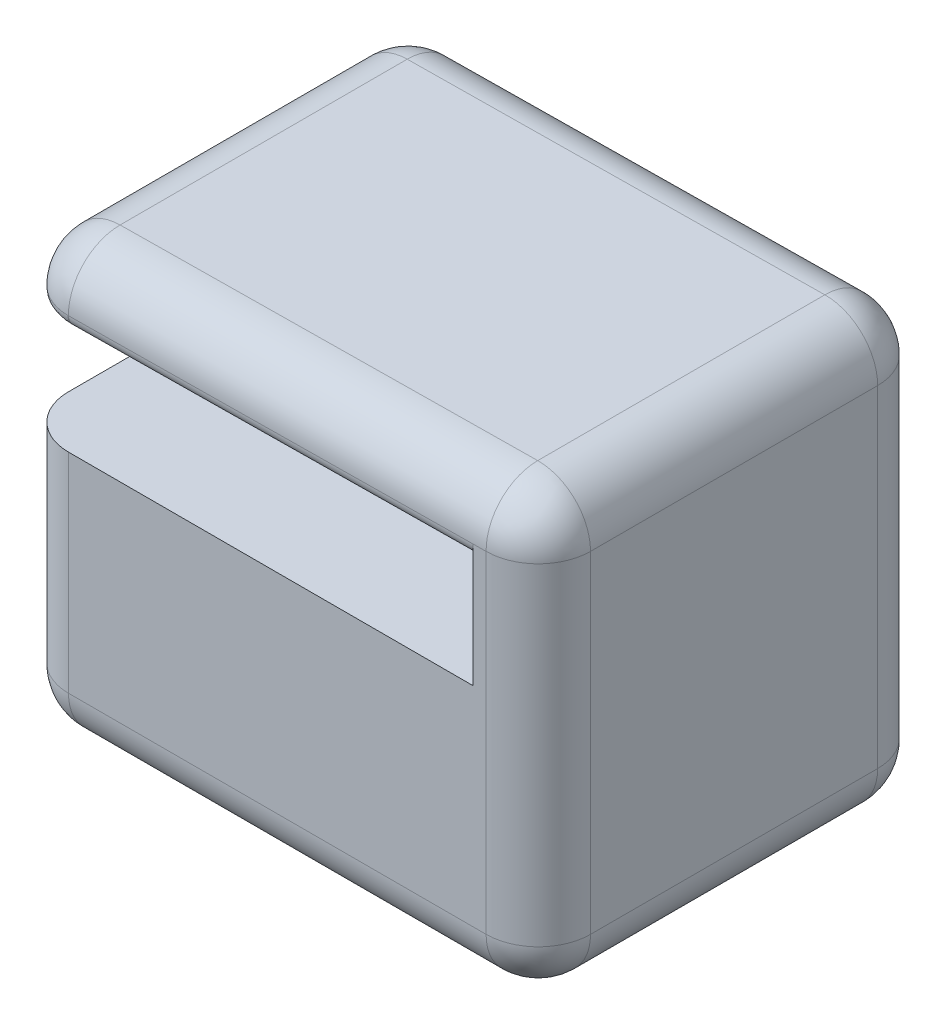
SolidWorks part; units mm, degrees
ref_plane "Front Plane" through (0, 0, 0) normal (0, 0, 1) x (1, 0, 0)
ref_plane "Top Plane" through (0, 0, 0) normal (0, 1, 0) x (1, 0, 0)
ref_plane "Right Plane" through (0, 0, 0) normal (1, 0, 0) x (0, 0, -1)
sketch "Sketch1" plane through (0, 0, 0) normal (0, 0, 1) x (1, 0, 0)
  line L1 (0, -10.6226) -> (-25.3983, -10.6226)
  line L2 (0, -10.6226) -> (0, 10.6226)
  line L3 (0, 10.6226) -> (-25.3983, 10.3324)
  line L4 (-25.3983, -10.6226) -> (-25.3983, 10.3324)
  line L5 (-25.3983, 7.1574) -> (-3.175, 7.1574) construction
  line L6 (-25.3983, 7.1574) -> (-25.3983, 2.0774) construction
  line L7 (-25.3983, 2.0774) -> (-3.175, 2.0774) construction
  line L8 (-3.175, 7.1574) -> (-3.175, 2.0774) construction
  line L12 (-25.3983, 7.1574) -> (-25.3983, 2.0774)
  line L13 (-25.3983, 2.0774) -> (-3.175, 2.0774)
  line L14 (-3.175, 2.0774) -> (-3.175, 7.4114)
  line L15 (-3.175, 7.4114) -> (-25.3983, 7.1574)
  point P6 (0, 0)
  dimension "D1" = 5.08
  dimension "D3" = 12.7
  dimension "D4" = 25.4
  dimension "D5" = 3.175
  dimension "D6" = 5.334
  dimension "D2" = 3.175
extrude "Boss-Extrude1" add sketch "Sketch1" along normal blind 19.05 contours L5 L8 L7 L4 L1 L2 L3 region at (-12.2497, -1.3816, 0)
sketch "Sketch4" plane through (0, -10.6226, 0) normal (0, 1, 0) x (1, 0, 0)
  line L0 (-12.7, 0) -> (-12.7, -19.05) construction
  line L1 (-25.3983, -19.05) -> (-25.3983, 0) construction
  circle A0 centre (-12.7, -19.05) radius 1.5
  circle A1 centre (-12.7, 0) radius 1.5
  point P4 (-12.7, -9.525)
  point P7 (-25.3983, -9.525)
  dimension "D1" = 3
  dimension "D2" = 19.05
  dimension "D3" = 9.525
extrude "Cut-Extrude2" [suppressed] cut sketch "Sketch4" along normal up to surface (12.7 mm away) up to face at (-14.2867, 2.0774, 9.525)
sketch "Sketch6" plane through (-0.1214, 10.6213, 0) normal (-0.0114, 0.9999, 0) x (0.9999, 0.0114, 0)
  line L0 (-12.6761, -19.05) -> (-12.6761, 0) construction
  line L6 (-3.1511, -19.05) -> (-3.1511, 0) construction
  line L7 (-25.2786, -19.05) -> (-25.2786, 0) construction
  circle A0 centre (-12.6761, -19.05) radius 1.5
  circle A1 centre (-12.6761, 0) radius 1.5
  point P6 (-12.6761, -9.525)
  point P9 (-25.2786, -9.525)
  dimension "D3" = 3
  dimension "D1" = 19.05
  dimension "D2" = 9.525
extrude "Cut-Extrude4" [suppressed] cut sketch "Sketch6" against normal up to surface (3.1745 mm away) up to face at (-14.2867, 7.2844, 9.525)
fillet "Fillet1" radius 2.54 14 edges at (-25.3983, -10.6226, 9.525) (-12.6992, -10.6226, 0) (-12.6992, 10.4775, 0) (-25.3983, 10.3324, 9.525) (-12.6992, 10.4775, 19.05) (-12.6992, -10.6226, 19.05) (0, -10.6226, 9.525) (0, 10.6226, 9.525) (0, 0, 0) (0, 0, 19.05) (-25.3983, -4.2726, 19.05) (-25.3983, -4.2726, 0) (-25.3983, 8.7449, 0) (-25.3983, 8.7449, 19.05)
sketch "Sketch2" plane through (-0.1214, 10.6213, 0) normal (-0.0114, 0.9999, 0) x (0.9999, 0.0114, 0)
  line L0 (-22.7675, -2.54) -> (-22.7675, -16.51) construction
  line L1 (-19.0826, 0.8) -> (-6.1326, 0.8)
  line L2 (-19.3326, 0.55) -> (-19.3326, -19.6)
  line L3 (-19.0826, -19.85) -> (-6.1326, -19.85)
  line L4 (-5.8826, 0.55) -> (-5.8826, -19.6)
  line L5 (-2.4478, -2.54) -> (-22.7675, -2.54) construction
  arc A0 (-6.1326, -19.85) -> (-5.8826, -19.6) centre (-6.1326, -19.6) ccw
  arc A1 (-19.3326, -19.6) -> (-19.0826, -19.85) centre (-19.0826, -19.6) ccw
  arc A2 (-6.1326, 0.8) -> (-5.8826, 0.55) centre (-6.1326, 0.55) cw
  arc A3 (-19.0826, 0.8) -> (-19.3326, 0.55) centre (-19.0826, 0.55) ccw
  point P4 (-19.3326, -9.525)
  point P7 (-22.7675, -9.525)
  point P9 (-12.6076, 0.8)
  point P12 (-12.6076, -2.54)
  point P14 (-5.8826, -19.85)
  point P16 (-5.8826, -19.85)
  point P20 (-5.8826, 0.8)
  point P23 (-19.3326, 0.8)
  dimension "D3" = 0.25
  dimension "D4" = 0.25
  dimension "D5" = 0.25
  dimension "D1" = 13.45
  dimension "D2" = 20.65
extrude "Cut-Extrude1" [suppressed] cut sketch "Sketch2" against normal blind 4.7625
fillet "Fillet2" radius 0.635 5 edges at (-13.0167, 7.2989, 19.05) (-24.6544, 7.1659, 18.3061) (-13.0167, 7.2989, 0) (-24.6544, 7.1659, 0.7439) (-25.3983, 7.1574, 9.525)
equation "\"bottomThickness\"= .220in"
equation "\"wallThickness\"= .118in"
equation "\"D6@Sketch1\"=\"bottomThickness\"-.01in"
equation "\"D1@Sketch1\"=\"bottomThickness\"-.02in"
